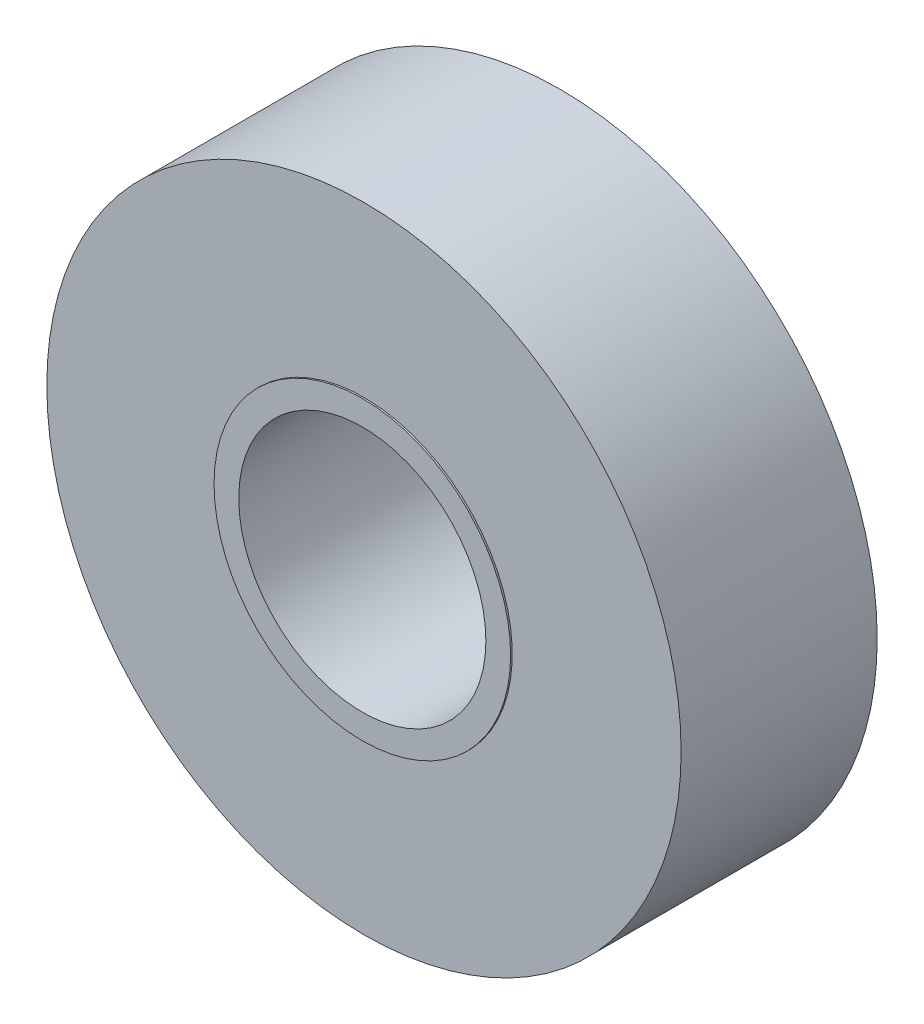
SolidWorks part; units mm, degrees
ref_plane "Alzado" through (0, 0, 0) normal (0, 0, 1) x (1, 0, 0)
ref_plane "Planta" through (0, 0, 0) normal (0, 1, 0) x (1, 0, 0)
ref_plane "Vista lateral" through (0, 0, 0) normal (1, 0, 0) x (0, 0, -1)
sketch "Croquis1" plane through (0, 0, 0) normal (0, 0, 1) x (1, 0, 0)
  circle A0 centre (0, 0) radius 7.5
  circle A1 centre (0, 0) radius 9
  circle A3 centre (0, 0) radius 9
  circle A4 centre (0, 0) radius 1.5
  circle A5 centre (0, 0) radius 7.4545
  circle A6 centre (0, 0) radius 7.5
  dimension "D1" = 15
  dimension "D2" = 18
  dimension "D3" = 3
extrude "Saliente-Extruir1" add sketch "Croquis1" along normal blind 12 contours A1 A0 region at (-8.7454, 0, 0)
sketch "Croquis2" plane through (0, 0, 0) normal (0, 0, 1) x (1, 0, 0)
  circle A0 centre (0, 0) radius 7.5
extrude "Saliente-Extruir2" add sketch "Croquis2" along normal blind 1 and the other way blind 0.1
sketch "Croquis3" plane through (0, 0, 0) normal (0, 0, 1) x (1, 0, 0)
  circle A0 centre (0, 0) radius 5.2
  circle A1 centre (0, 0) radius 1.5
  dimension "D1" = 10.4
  dimension "D2" = 3
extrude "Saliente-Extruir4" add sketch "Croquis3" against normal blind 3 contours A0 | A1
sketch "Croquis4" plane through (0, 0, 0) normal (0, 0, -1) x (-1, 0, 0)
  circle A0 centre (0, 0) radius 9
  circle A1 centre (0, 0) radius 19.25
  dimension "D1" = 38.5
extrude "Saliente-Extruir5" add sketch "Croquis4" against normal blind 11.9
sketch "Croquis6" plane through (0, 0, -3) normal (0, 0, -1) x (-1, 0, 0)
  circle A0 centre (0, 0) radius 1.5
extrude "Cortar-Extruir1" cut sketch "Croquis6" against normal blind 10
sketch "Croquis7" plane through (0, 0, 0) normal (0, 1, 0) x (1, 0, 0)
  line L0 (0, 3) -> (0, 0.1) construction
  line L1 (5.2, 3) -> (-5.2, 3) construction
  line L2 (7.5, 0.1) -> (-7.5, 0.1) construction
  circle A0 centre (0, 1.55) radius 1
  dimension "D1" = 2
extrude "Cortar-Extruir2" cut sketch "Croquis7" along normal blind 10 and the other way blind 10
